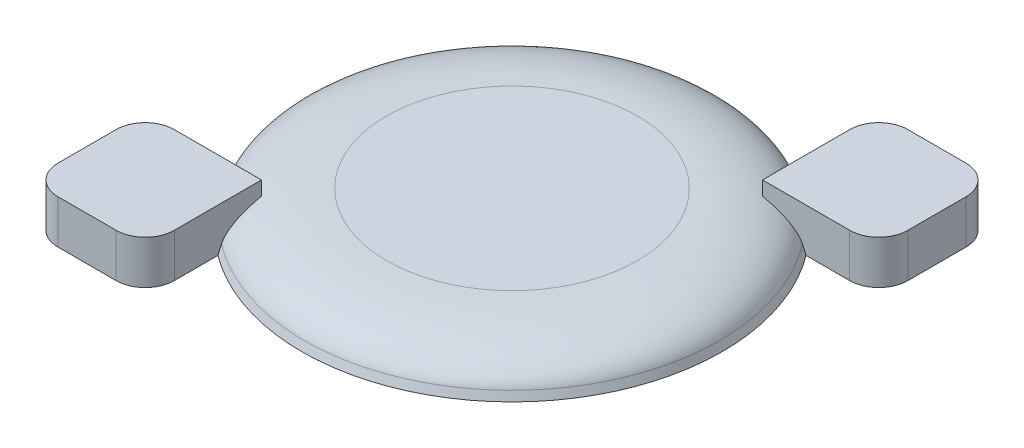
SolidWorks part; units mm, degrees
material "ABS"
ref_plane "Front Plane" through (0, 0, 0) normal (0, 0, 1) x (1, 0, 0)
ref_plane "Top Plane" through (0, 0, 0) normal (0, 1, 0) x (1, 0, 0)
ref_plane "Right Plane" through (0, 0, 0) normal (1, 0, 0) x (0, 0, -1)
sketch "Sketch1" plane through (0, 0, 0) normal (0, 1, 0) x (1, 0, 0)
  line L1 (-17.5, 17.5) -> (17.5, 17.5)
  line L2 (-17.5, 17.5) -> (-17.5, -17.5)
  line L3 (-17.5, -17.5) -> (17.5, -17.5)
  line L4 (17.5, 17.5) -> (17.5, -17.5)
  line L5 (-17.5, 17.5) -> (17.5, -17.5) construction
  line L6 (-17.5, -17.5) -> (17.5, 17.5) construction
  point P0 (0, 0)
  dimension "D1" = 35
sketch "Sketch2" plane through (0, 0, 0) normal (0, 1, 0) x (1, 0, 0)
  circle A0 centre (0, 0) radius 14.4638
extrude "Boss-Extrude1" add sketch "Sketch2" along normal blind 2.5 draft 20
fillet "Fillet1" radius 4 1 edges at (0, 2.5, 13.5539)
sketch "Sketch4" plane through (0, 0, 0) normal (0, 1, 0) x (1, 0, 0)
  line L0 (-17.5, -17.5) -> (17.5, 17.5) construction
  line L1 (-16.6164, -16.6164) -> (-8.6164, -16.6164)
  line L2 (-16.6164, -16.6164) -> (-16.6164, -8.6164)
  line L3 (-16.6164, -8.6164) -> (-8.6164, -8.6164)
  line L4 (-8.6164, -16.6164) -> (-8.6164, -8.6164)
  line L5 (-16.6164, -16.6164) -> (-8.6164, -8.6164) construction
  line L6 (-16.6164, -8.6164) -> (-8.6164, -16.6164) construction
  point P0 (-12.6164, -12.6164)
  point P5 (0, 0)
  dimension "D1" = 8
extrude "Boss-Extrude2" add sketch "Sketch4" along normal blind 3
fillet "Fillet2" radius 2 3 edges at (-8.6164, 1.5, 16.6164) (-16.6164, 1.5, 16.6164) (-16.6164, 1.5, 8.6164)
pattern_circular "CirPattern1" count 4 over 360 about axis through (0, 0, 0) along (0, 1, 0) of "Fillet2", "Boss-Extrude2"
